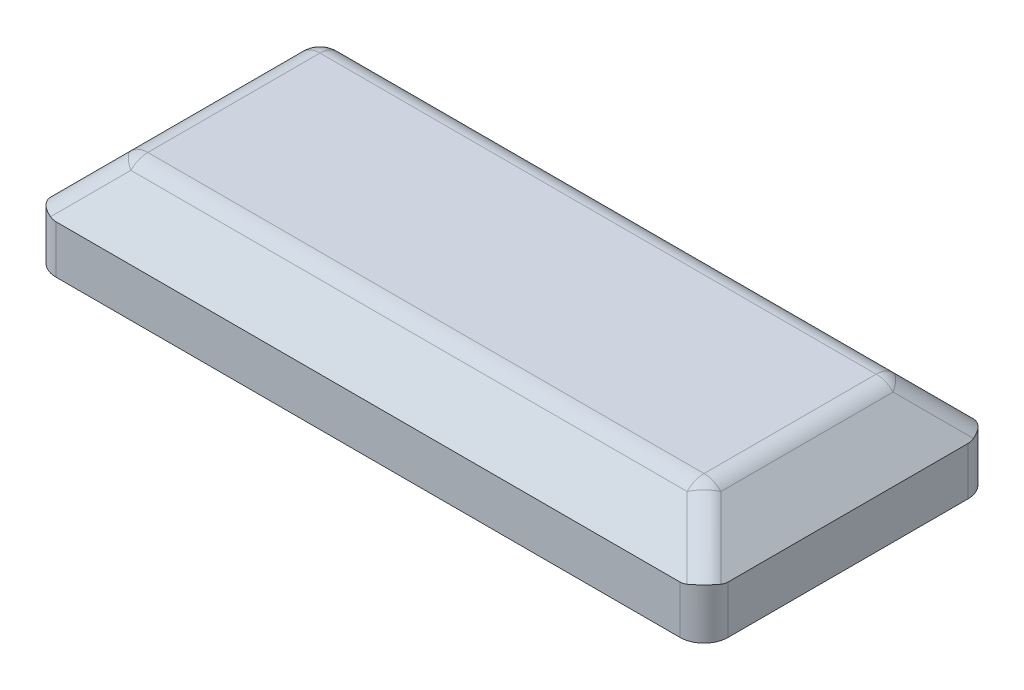
SolidWorks part; units mm, degrees
ref_plane "Front Plane" through (0, 0, 0) normal (0, 0, 1) x (1, 0, 0)
ref_plane "Top Plane" through (0, 0, 0) normal (0, 1, 0) x (1, 0, 0)
ref_plane "Right Plane" through (0, 0, 0) normal (1, 0, 0) x (0, 0, -1)
sketch "Sketch1" plane through (0, 0, 0) normal (0, 1, 0) x (1, 0, 0)
  line L1 (-70, -30) -> (70, -30)
  line L2 (-70, -30) -> (-70, 30)
  line L3 (-70, 30) -> (70, 30)
  line L4 (70, -30) -> (70, 30)
  line L5 (-70, -30) -> (70, 30) construction
  line L6 (-70, 30) -> (70, -30) construction
  point P0 (0, 0)
  dimension "D1" = 140
  dimension "D2" = 60
extrude "Boss-Extrude1" add sketch "Sketch1" along normal blind 10
sketch "Sketch2" plane through (0, 10, 0) normal (0, 1, 0) x (1, 0, 0)
  line L4 (70, -30) -> (70, 30)
  line L5 (70, 30) -> (-70, 30)
  line L6 (-70, 30) -> (-70, -30)
  line L7 (-70, -30) -> (70, -30)
  line L8 (70, -30) -> (70, 30)
  line L9 (70, 30) -> (-70, 30)
  line L10 (-70, 30) -> (-70, -30)
  line L11 (-70, -30) -> (70, -30)
  dimension "D1" = 0
extrude "Boss-Extrude2" add sketch "Sketch2" along normal blind 10 draft 45
fillet "Fillet1" radius 5 12 edges at (70, 5, -30) (70, 5, 30) (-70, 5, 30) (-70, 5, -30) (-60, 20, 0) (0, 20, -20) (60, 20, 0) (0, 20, 20) (-65, 15, -25) (65, 15, -25) (65, 15, 25) (-65, 15, 25)
